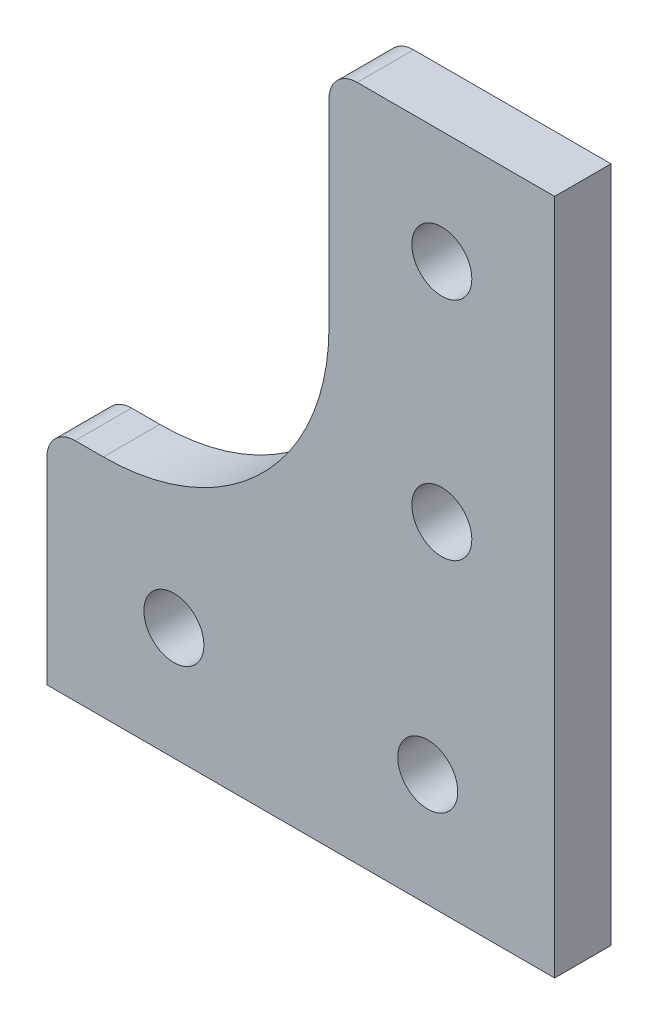
SolidWorks part; units mm, degrees
ref_plane "Front Plane" through (0, 0, 0) normal (0, 0, 1) x (1, 0, 0)
ref_plane "Top Plane" through (0, 0, 0) normal (0, 1, 0) x (1, 0, 0)
ref_plane "Right Plane" through (0, 0, 0) normal (1, 0, 0) x (0, 0, -1)
sketch "Sketch1" plane through (0, 0, 0) normal (0, 0, 1) x (1, 0, 0)
  line L0 (-28.575, -12.7) -> (28.575, -12.7)
  line L1 (28.575, -12.7) -> (28.575, 63.5)
  line L2 (28.575, 63.5) -> (3.175, 63.5)
  line L3 (3.175, 63.5) -> (3.175, 12.7)
  line L4 (3.175, 12.7) -> (-28.575, 12.7)
  line L5 (-28.575, 12.7) -> (-28.575, -12.7)
  point P6 (0, -12.7)
  point P7 (-28.575, 0)
  dimension "D1" = 25.4
  dimension "D2" = 25.4
  dimension "D3" = 50.8
  dimension "D4" = 28.575
extrude "Boss-Extrude1" add sketch "Sketch1" along normal mid plane 6.35
sketch "Sketch2" plane through (0, 0, 3.175) normal (0, 0, 1) x (1, 0, 0)
  circle A0 centre (15.875, 25.4) radius 3.3782 construction
  circle A1 centre (15.875, 50.8) radius 3.3782 construction
  circle A2 centre (15.875, 25.4) radius 3.3782
  circle A3 centre (15.875, 50.8) radius 3.3782
extrude "Cut-Extrude1" cut sketch "Sketch2" against normal through all
sketch "Sketch3" plane through (0, 0, 3.175) normal (0, 0, 1) x (1, 0, 0)
  line L0 (-14.2875, 0) -> (14.2875, 0) construction
  circle A0 centre (-14.2875, 0) radius 3.3782
  circle A1 centre (14.2875, 0) radius 3.3782
  point P5 (0, 0)
  dimension "D1" = 6.7564
  dimension "D2" = 6.7564
  dimension "D3" = 28.575
extrude "Cut-Extrude2" cut sketch "Sketch3" against normal through all
fillet "Fillet1" radius 25.4 1 edges at (3.175, 12.7, 0)
fillet "Fillet2" radius 3.175 2 edges at (-28.575, 12.7, 0) (3.175, 63.5, 0)
